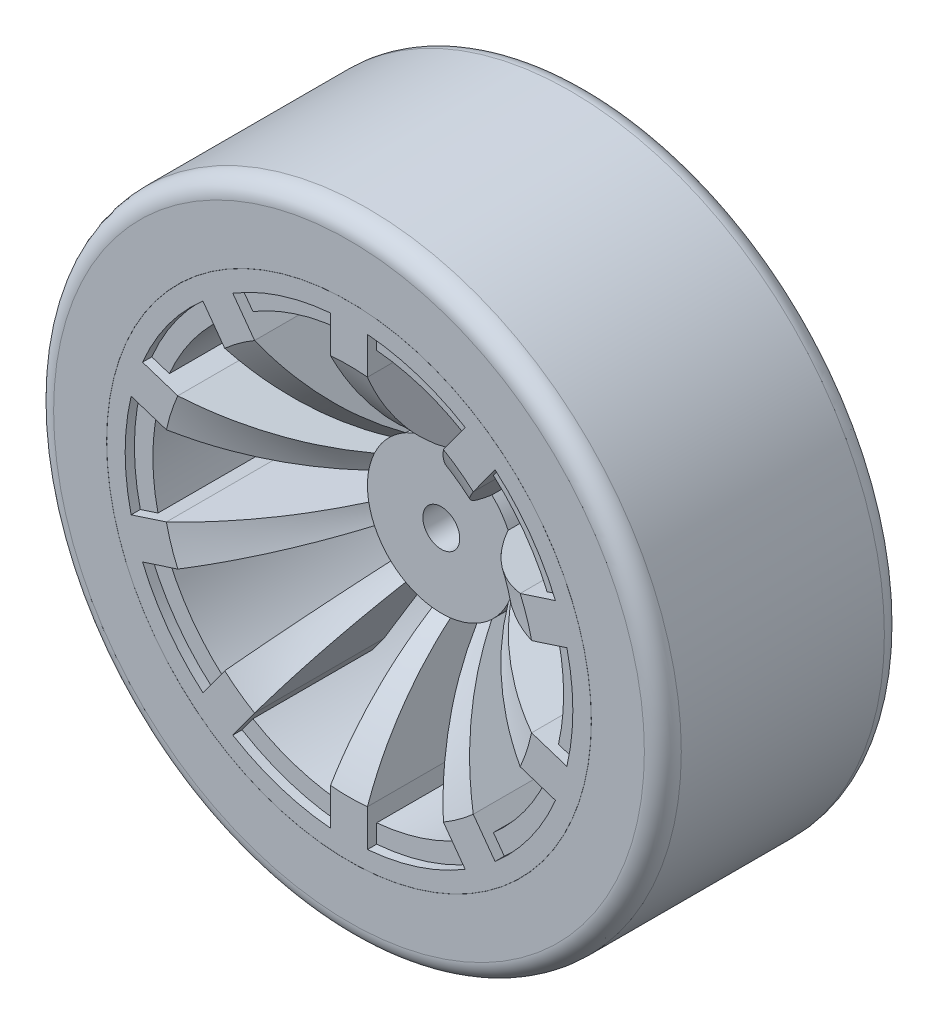
SolidWorks part; units mm, degrees
ref_plane "Front Plane" through (0, 0, 0) normal (0, 0, 1) x (1, 0, 0)
ref_plane "Top Plane" through (0, 0, 0) normal (0, 1, 0) x (1, 0, 0)
ref_plane "Right Plane" through (0, 0, 0) normal (1, 0, 0) x (0, 0, -1)
sketch "Sketch2" plane through (0, 0, 0) normal (0, 1, 0) x (1, 0, 0)
  line L0 (0, 13) -> (0, -13) construction
  line L1 (-26.25, 13) -> (-24.25, 13)
  line L2 (-26.25, 13) -> (-26.25, -13)
  line L3 (-26.25, -13) -> (-20.25, -13)
  line L5 (-8, -3) -> (-2, -3)
  line L6 (-2, 5) -> (-8, 5)
  line L7 (-20.25, -13) -> (-8, -3) construction
  line L8 (-13.4926, -8.7747) -> (-14.125, -8) construction
  line L10 (-22.25, 1) -> (-22.25, 11)
  line L11 (-8, 1) -> (-22.25, 1)
  line L12 (-24.25, 13) -> (-22.25, 11)
  line L13 (-8, 1) -> (-8, 5)
  line L16 (-2, 5) -> (-2, -3)
  arc A0 (-20.25, -13) -> (-8, -3) centre (-33.5755, 15.8269) ccw
  point P0 (0, 0)
  point P8 (-13.4926, -8.7747)
  point P16 (-20.25, -13)
  dimension "D1" = 45
  dimension "D2" = 4
  dimension "D3" = 10
  dimension "D4" = 8
  dimension "D5" = 26
  dimension "D6" = 6
  dimension "D7" = 4
  dimension "D8" = 8
  dimension "D9" = 1
  dimension "D10" = 2
  dimension "D12" = 2
  dimension "D13" = 26.25
revolve "Revolve1" add sketch "Sketch2" angle 360 about L0
sketch "Sketch4" plane through (0, 0, 13) normal (0, 0, 1) x (1, 0, 0)
  line L0 (0, 0) -> (0, 20.25) construction
  line L1 (0, 0) -> (11.9027, 16.3826) construction
  line L2 (0, 0) -> (19.2589, 6.2576) construction
  line L3 (0, 0) -> (19.2589, -6.2576) construction
  line L4 (0, 0) -> (11.9027, -16.3826) construction
  line L5 (0, 0) -> (0, -20.25) construction
  line L6 (0, 0) -> (-11.9027, -16.3826) construction
  line L7 (0, 0) -> (-19.2589, -6.2576) construction
  line L8 (0, 0) -> (-19.2589, 6.2576) construction
  line L9 (0, 0) -> (-11.9027, 16.3826) construction
  line L10 (-2, 20.151) -> (-1, 7.9373)
  line L11 (2, 20.151) -> (1, 7.9373)
  line L12 (10.2264, 17.4781) -> (3.8564, 7.0092)
  line L13 (13.4625, 15.1269) -> (5.4744, 5.8336)
  line L14 (18.5467, 8.1291) -> (7.2398, 3.4038)
  line L15 (19.7828, 4.3249) -> (7.8578, 1.5017)
  line L16 (19.7828, -4.3249) -> (7.8578, -1.5017)
  line L17 (18.5467, -8.1291) -> (7.2398, -3.4038)
  line L18 (13.4625, -15.1269) -> (5.4744, -5.8336)
  line L19 (10.2264, -17.4781) -> (3.8564, -7.0092)
  line L20 (2, -20.151) -> (1, -7.9373)
  line L21 (-2, -20.151) -> (-1, -7.9373)
  line L22 (-10.2264, -17.4781) -> (-3.8564, -7.0092)
  line L23 (-13.4625, -15.1269) -> (-5.4744, -5.8336)
  line L24 (-18.5467, -8.1291) -> (-7.2398, -3.4038)
  line L25 (-19.7828, -4.3249) -> (-7.8578, -1.5017)
  line L26 (-19.7828, 4.3249) -> (-7.8578, 1.5017)
  line L27 (-18.5467, 8.1291) -> (-7.2398, 3.4038)
  line L28 (-13.4625, 15.1269) -> (-5.4744, 5.8336)
  line L29 (-10.2264, 17.4781) -> (-3.8564, 7.0092)
  circle A0 centre (0, 0) radius 20.25 construction
  arc A1 (-13.4625, 15.1269) -> (-18.5467, 8.1291) centre (0, 0) ccw
  circle A2 centre (0, 0) radius 8 construction
  arc A3 (-5.4744, 5.8336) -> (-7.2398, 3.4038) centre (0, 0) ccw
  arc A4 (-1, 7.9373) -> (-3.8564, 7.0092) centre (0, 0) ccw
  arc A5 (3.8564, 7.0092) -> (1, 7.9373) centre (0, 0) ccw
  arc A6 (7.2398, 3.4038) -> (5.4744, 5.8336) centre (0, 0) ccw
  arc A7 (-7.8578, 1.5017) -> (-7.8578, -1.5017) centre (0, 0) ccw
  arc A8 (-7.2398, -3.4038) -> (-5.4744, -5.8336) centre (0, 0) ccw
  arc A9 (-3.8564, -7.0092) -> (-1, -7.9373) centre (0, 0) ccw
  arc A10 (1, -7.9373) -> (3.8564, -7.0092) centre (0, 0) ccw
  arc A11 (5.4744, -5.8336) -> (7.2398, -3.4038) centre (0, 0) ccw
  arc A12 (7.8578, -1.5017) -> (7.8578, 1.5017) centre (0, 0) ccw
  arc A13 (-19.7828, 4.3249) -> (-19.7828, -4.3249) centre (0, 0) ccw
  arc A14 (-18.5467, -8.1291) -> (-13.4625, -15.1269) centre (0, 0) ccw
  arc A15 (-10.2264, -17.4781) -> (-2, -20.151) centre (0, 0) ccw
  arc A16 (2, -20.151) -> (10.2264, -17.4781) centre (0, 0) ccw
  arc A17 (13.4625, -15.1269) -> (18.5467, -8.1291) centre (0, 0) ccw
  arc A18 (19.7828, -4.3249) -> (19.7828, 4.3249) centre (0, 0) ccw
  arc A19 (18.5467, 8.1291) -> (13.4625, 15.1269) centre (0, 0) ccw
  arc A20 (10.2264, 17.4781) -> (2, 20.151) centre (0, 0) ccw
  arc A21 (-2, 20.151) -> (-10.2264, 17.4781) centre (0, 0) ccw
  point P17 (0, 0)
  point P61 (0, 0)
  dimension "D2" = 2
  dimension "D3" = 4
  dimension "D1" = 10
  dimension "D4" = 10
extrude "Cut-Extrude1" cut sketch "Sketch4" against normal through all
sketch "Sketch6" plane through (0, 0, 13) normal (0, 0, 1) x (1, 0, 0)
  line L0 (2, 20.151) -> (2, 24.1674)
  line L1 (-2, 20.151) -> (-2, 24.1674)
  line L2 (0, 1.046) -> (0, 29.7456) construction
  line L3 (10.2264, 17.4781) -> (12.5872, 20.7274)
  line L4 (13.4625, 15.1269) -> (15.8233, 18.3763)
  line L5 (18.5467, 8.1291) -> (22.3665, 9.3702)
  line L6 (19.7828, 4.3249) -> (23.6026, 5.566)
  line L7 (19.7828, -4.3249) -> (23.6026, -5.566)
  line L8 (18.5467, -8.1291) -> (22.3665, -9.3702)
  line L9 (13.4625, -15.1269) -> (15.8233, -18.3763)
  line L10 (10.2264, -17.4781) -> (12.5872, -20.7274)
  line L11 (2, -20.151) -> (2, -24.1674)
  line L12 (-2, -20.151) -> (-2, -24.1674)
  line L13 (-10.2264, -17.4781) -> (-12.5872, -20.7274)
  line L14 (-13.4625, -15.1269) -> (-15.8233, -18.3763)
  line L15 (-18.5467, -8.1291) -> (-22.3665, -9.3702)
  line L16 (-19.7828, -4.3249) -> (-23.6026, -5.566)
  line L17 (-19.7828, 4.3249) -> (-23.6026, 5.566)
  line L18 (-18.5467, 8.1291) -> (-22.3665, 9.3702)
  line L19 (-13.4625, 15.1269) -> (-15.8233, 18.3763)
  line L20 (-10.2264, 17.4781) -> (-12.5872, 20.7274)
  arc A2 (-15.8233, 18.3763) -> (-22.3665, 9.3702) centre (0, 0) ccw
  arc A4 (-13.4625, 15.1269) -> (-18.5467, 8.1291) centre (0, 0) ccw
  arc A5 (-2, 20.151) -> (-10.2264, 17.4781) centre (0, 0) ccw
  arc A6 (-2, 24.1674) -> (-12.5872, 20.7274) centre (0, 0) ccw
  arc A7 (12.5872, 20.7274) -> (2, 24.1674) centre (0, 0) ccw
  arc A8 (10.2264, 17.4781) -> (2, 20.151) centre (0, 0) ccw
  arc A9 (18.5467, 8.1291) -> (13.4625, 15.1269) centre (0, 0) ccw
  arc A10 (22.3665, 9.3702) -> (15.8233, 18.3763) centre (0, 0) ccw
  arc A11 (19.7828, -4.3249) -> (19.7828, 4.3249) centre (0, 0) ccw
  arc A12 (23.6026, -5.566) -> (23.6026, 5.566) centre (0, 0) ccw
  arc A13 (13.4625, -15.1269) -> (18.5467, -8.1291) centre (0, 0) ccw
  arc A14 (15.8233, -18.3763) -> (22.3665, -9.3702) centre (0, 0) ccw
  arc A15 (2, -20.151) -> (10.2264, -17.4781) centre (0, 0) ccw
  arc A16 (2, -24.1674) -> (12.5872, -20.7274) centre (0, 0) ccw
  arc A17 (-10.2264, -17.4781) -> (-2, -20.151) centre (0, 0) ccw
  arc A18 (-12.5872, -20.7274) -> (-2, -24.1674) centre (0, 0) ccw
  arc A19 (-18.5467, -8.1291) -> (-13.4625, -15.1269) centre (0, 0) ccw
  arc A20 (-22.3665, -9.3702) -> (-15.8233, -18.3763) centre (0, 0) ccw
  arc A21 (-23.6026, 5.566) -> (-23.6026, -5.566) centre (0, 0) ccw
  arc A22 (-19.7828, 4.3249) -> (-19.7828, -4.3249) centre (0, 0) ccw
  point P53 (0, 0)
  dimension "D2" = 10
  dimension "D3" = 48.5
  dimension "D4" = 40.5
extrude "Cut-Extrude2" cut sketch "Sketch6" against normal blind 1
sketch "Sketch8" plane through (0, 0, 12) normal (0, 0, 1) x (1, 0, 0)
  line L0 (-2, 20.151) -> (-2, 22.1599)
  line L2 (2, 20.151) -> (2, 22.1599)
  line L4 (10.2264, 17.4781) -> (11.4072, 19.1033)
  line L5 (13.4625, 15.1269) -> (14.6433, 16.7522)
  line L6 (18.5467, 8.1291) -> (20.4573, 8.7499)
  line L7 (19.7828, 4.3249) -> (21.6934, 4.9457)
  line L8 (19.7828, -4.3249) -> (21.6934, -4.9457)
  line L9 (18.5467, -8.1291) -> (20.4573, -8.7499)
  line L10 (13.4625, -15.1269) -> (14.6433, -16.7522)
  line L11 (10.2264, -17.4781) -> (11.4072, -19.1033)
  line L12 (2, -20.151) -> (2, -22.1599)
  line L13 (-2, -20.151) -> (-2, -22.1599)
  line L14 (-10.2264, -17.4781) -> (-11.4072, -19.1033)
  line L15 (-13.4625, -15.1269) -> (-14.6433, -16.7522)
  line L16 (-18.5467, -8.1291) -> (-20.4573, -8.7499)
  line L17 (-19.7828, -4.3249) -> (-21.6934, -4.9457)
  line L18 (-19.7828, 4.3249) -> (-21.6934, 4.9457)
  line L19 (-18.5467, 8.1291) -> (-20.4573, 8.7499)
  line L20 (-13.4625, 15.1269) -> (-14.6433, 16.7522)
  line L21 (-10.2264, 17.4781) -> (-11.4072, 19.1033)
  arc A0 (-2, 20.151) -> (-10.2264, 17.4781) centre (0, 0) ccw
  arc A1 (-2, 22.1599) -> (-11.4072, 19.1033) centre (0, 0) ccw
  arc A2 (-13.4625, 15.1269) -> (-18.5467, 8.1291) centre (0, 0) ccw
  arc A3 (-14.6433, 16.7522) -> (-20.4573, 8.7499) centre (0, 0) ccw
  arc A4 (-19.7828, 4.3249) -> (-19.7828, -4.3249) centre (0, 0) ccw
  arc A5 (-21.6934, 4.9457) -> (-21.6934, -4.9457) centre (0, 0) ccw
  arc A6 (-20.4573, -8.7499) -> (-14.6433, -16.7522) centre (0, 0) ccw
  arc A7 (-18.5467, -8.1291) -> (-13.4625, -15.1269) centre (0, 0) ccw
  arc A8 (-10.2264, -17.4781) -> (-2, -20.151) centre (0, 0) ccw
  arc A9 (-11.4072, -19.1033) -> (-2, -22.1599) centre (0, 0) ccw
  arc A10 (2, -20.151) -> (10.2264, -17.4781) centre (0, 0) ccw
  arc A11 (2, -22.1599) -> (11.4072, -19.1033) centre (0, 0) ccw
  arc A12 (13.4625, -15.1269) -> (18.5467, -8.1291) centre (0, 0) ccw
  arc A13 (14.6433, -16.7522) -> (20.4573, -8.7499) centre (0, 0) ccw
  arc A14 (19.7828, -4.3249) -> (19.7828, 4.3249) centre (0, 0) ccw
  arc A15 (21.6934, -4.9457) -> (21.6934, 4.9457) centre (0, 0) ccw
  arc A16 (18.5467, 8.1291) -> (13.4625, 15.1269) centre (0, 0) ccw
  arc A17 (20.4573, 8.7499) -> (14.6433, 16.7522) centre (0, 0) ccw
  arc A18 (10.2264, 17.4781) -> (2, 20.151) centre (0, 0) ccw
  arc A19 (11.4072, 19.1033) -> (2, 22.1599) centre (0, 0) ccw
  point P47 (0, 0)
  dimension "D1" = 44.5
  dimension "D3" = 10
extrude "Cut-Extrude3" cut sketch "Sketch8" against normal through all
sketch "Sketch9" plane through (0, 0, 0) normal (0, 1, 0) x (1, 0, 0)
  line L0 (0, 20.6875) -> (0, -20.2062) construction
  line L1 (-26.26, 13) -> (-25.7616, 12.5016)
  line L2 (-26.26, 13) -> (-34, 13)
  line L3 (-25.7616, 12.5016) -> (-25.7616, -12.5016)
  line L4 (-26.26, -13) -> (-34, -13)
  line L5 (-34, 13) -> (-34, -13)
  line L6 (-34, 0) -> (26.25, 0) construction
  line L7 (26.25, -13) -> (26.25, 13) construction
  line L8 (-26.26, -13) -> (-25.7616, -12.5016)
  dimension "D1" = 26
  dimension "D2" = 34
  dimension "D3" = 45
revolve "Revolve2" add sketch "Sketch9" angle 360 about L0
fillet "Fillet1" radius 2 2 edges at (-34, 0, 13) (-34, 0, -13)
sketch "Sketch10" plane through (0, 0, -5) normal (0, 0, -1) x (-1, 0, 0)
  line L0 (0, 0) -> (-9.5997, 0) construction
  line L1 (-3.4641, 6) -> (-6.9282, 0)
  line L2 (-6.9282, 0) -> (-3.4641, -6)
  line L3 (-3.4641, -6) -> (3.4641, -6)
  line L4 (3.4641, -6) -> (6.9282, 0)
  line L5 (6.9282, 0) -> (3.4641, 6)
  line L6 (3.4641, 6) -> (-3.4641, 6)
  circle A0 centre (0, 0) radius 6 construction
  dimension "D1" = 12
extrude "Boss-Extrude1" add sketch "Sketch10" along normal blind 1
sketch "Sketch11" plane through (0, 0, -6) normal (0, 0, -1) x (-1, 0, 0)
  circle A0 centre (0, 0) radius 5.5
  dimension "D1" = 11
extrude "Boss-Extrude2" add sketch "Sketch11" along normal blind 11
